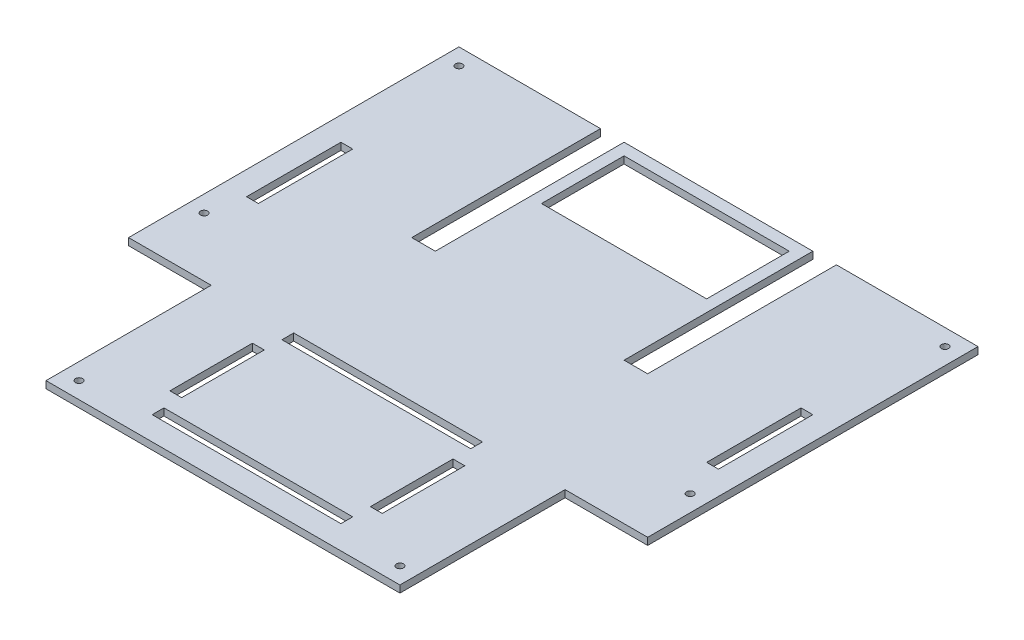
SolidWorks part; units mm, degrees
material "Pine"
ref_plane "Front Plane" through (0, 0, 0) normal (0, 0, 1) x (1, 0, 0)
ref_plane "Top Plane" through (0, 0, 0) normal (0, 1, 0) x (1, 0, 0)
ref_plane "Right Plane" through (0, 0, 0) normal (1, 0, 0) x (0, 0, -1)
sketch "Sketch4" plane through (0, 0, 0) normal (0, 1, 0) x (1, 0, 0)
  line L1 (0, 0) -> (-220, 0)
  line L2 (0, 0) -> (0, 210)
  line L3 (0, 210) -> (-220, 210)
  line L4 (-220, 0) -> (-220, 210)
  dimension "D1" = 220
  dimension "D2" = 210
extrude "Boss-Extrude1" add sketch "Sketch4" along normal blind 3
sketch "Sketch5" plane through (0, 3, 0) normal (0, 1, 0) x (1, 0, 0)
  line L1 (-220, 0) -> (-185, 0)
  line L2 (-220, 0) -> (-220, 70)
  line L3 (-220, 70) -> (-185, 70)
  line L4 (-185, 0) -> (-185, 70)
  dimension "D1" = 35
  dimension "D2" = 70
extrude "Cut-Extrude1" cut sketch "Sketch5" against normal blind 3
sketch "Sketch6" plane through (0, 3, 0) normal (0, 1, 0) x (1, 0, 0)
  line L1 (0, 0) -> (-35, 0)
  line L2 (0, 0) -> (0, 70)
  line L3 (0, 70) -> (-35, 70)
  line L4 (-35, 0) -> (-35, 70)
  dimension "D1" = 35
  dimension "D2" = 70
extrude "Cut-Extrude2" cut sketch "Sketch6" against normal blind 3
sketch "Sketch12" plane through (0, 3, 0) normal (0, 1, 0) x (1, 0, 0)
  line L2 (-35, 88) -> (-35, 80)
  line L5 (-35, 70) -> (-35, 0) construction
  dimension "D4" = 0
extrude "Cut-Extrude8" cut sketch "Sketch12" against normal blind 3 rebuild error yes
sketch "Sketch13" plane through (0, 3, 0) normal (0, 1, 0) x (1, 0, 0)
  line L4 (-215, 80) -> (-215, 88)
  dimension "D1" = 8
extrude "Cut-Extrude9" cut sketch "Sketch13" against normal blind 3 rebuild error yes
sketch "Sketch14" plane through (0, 3, 0) normal (0, 1, 0) x (1, 0, 0)
  line L0 (-110, 210) -> (-110, 0)
  line L1 (0, 210) -> (-220, 210) construction
  line L2 (-185, 0) -> (-35, 0) construction
sketch "Sketch22" plane through (0, 3, 0) normal (0, 1, 0) x (1, 0, 0)
  line L0 (-185, 0) -> (-185, 70) construction
  line L1 (-185, 0) -> (-35, 0) construction
  circle A0 centre (-178, 7) radius 1.5
  dimension "D1" = 7
  dimension "D2" = 7
sketch "Sketch24" plane through (0, 3, 0) normal (0, 1, 0) x (1, 0, 0)
  line L2 (-185, 0) -> (-35, 0) construction
  line L3 (-35, 70) -> (-35, 0) construction
  circle A0 centre (-42, 7) radius 1.5
  dimension "D1" = 7
  dimension "D2" = 7
sketch "Sketch25" plane through (0, 3, 0) normal (0, 1, 0) x (1, 0, 0)
  line L2 (0, 210) -> (-220, 210) construction
  line L3 (0, 70) -> (0, 210) construction
  circle A0 centre (-7, 203) radius 1.5
  dimension "D1" = 7
  dimension "D2" = 7
sketch "Sketch26" plane through (0, 3, 0) normal (0, 1, 0) x (1, 0, 0)
  line L2 (0, 210) -> (-220, 210) construction
  line L3 (-220, 210) -> (-220, 70) construction
  circle A0 centre (-213, 203) radius 1.5
  dimension "D1" = 7
  dimension "D2" = 7
extrude "Cut-Extrude15" cut sketch "Sketch22" against normal blind 3
extrude "Cut-Extrude16" cut sketch "Sketch26" against normal blind 3 contours A0
extrude "Cut-Extrude17" cut sketch "Sketch24" against normal blind 3
extrude "Cut-Extrude18" cut sketch "Sketch25" against normal blind 3
sketch "Sketch27" plane through (0, 3, 0) normal (0, 1, 0) x (1, 0, 0)
  line L0 (-220, 210) -> (-220, 70) construction
  line L1 (-185, 88) -> (-215, 88) construction
  circle A0 centre (-213, 95) radius 1.5
  dimension "D1" = 7
  dimension "D2" = 7
extrude "Cut-Extrude19" cut sketch "Sketch27" against normal blind 3
sketch "Sketch28" plane through (0, 3, 0) normal (0, 1, 0) x (1, 0, 0)
  line L0 (-5, 88) -> (-35, 88) construction
  line L1 (0, 70) -> (0, 210) construction
  circle A0 centre (-7, 95) radius 1.5
  dimension "D1" = 7
  dimension "D2" = 7
extrude "Cut-Extrude20" cut sketch "Sketch28" against normal blind 3
sketch "Sketch55" plane through (0, 3, 0) normal (0, 1, 0) x (1, 0, 0)
  line L1 (-52.038, 199.3694) -> (-7.038, 199.3694)
  line L2 (-52.038, 199.3694) -> (-52.038, 174.3694)
  line L3 (-52.038, 174.3694) -> (-7.038, 174.3694)
  line L4 (-7.038, 199.3694) -> (-7.038, 174.3694)
  dimension "D1" = 45
  dimension "D2" = 25
sketch "Sketch56" plane through (0, 3, 0) normal (0, 1, 0) x (1, 0, 0)
  line L0 (0, 210) -> (-220, 210) construction
  line L1 (-70, 210) -> (-60, 210)
  line L2 (-70, 210) -> (-70, 130)
  line L3 (-70, 130) -> (-60, 130)
  line L4 (-60, 210) -> (-60, 130)
  line L5 (0, 210) -> (-220, 210) construction
  line L6 (-110, 210) -> (-110, 0)
  line L7 (-185, 0) -> (-35, 0) construction
  line L8 (-150, 130) -> (-160, 130)
  line L9 (-150, 210) -> (-150, 130)
  line L10 (-150, 210) -> (-160, 210)
  line L11 (-160, 210) -> (-160, 130)
  line L13 (-145, 205) -> (-75, 205)
  line L14 (-145, 205) -> (-145, 170)
  line L15 (-145, 170) -> (-75, 170)
  line L16 (-75, 205) -> (-75, 170)
  point P6 (-110, 210)
  line M10 (0, 210) -> (-220, 210)
  dimension "D1" = 40
  dimension "D2" = 10
  dimension "D3" = 80
  dimension "D4" = 70
  dimension "D5" = 35
  dimension "D6" = 5
  dimension "D7" = 35
extrude "Cut-Extrude21" cut sketch "Sketch56" against normal blind 3 contours L14 L15 L6 L13 | L16 L13 L6 L15 | L11 L8 L9 M10 | L2 L3 L4 L1 region at (-92.5, 3, -187.5) region at (-127.5, 3, -187.5) region at (-155, 3, -170)
sketch "Sketch57" plane through (0, 3, 0) normal (0, 1, 0) x (1, 0, 0)
  line L0 (-185, 0) -> (-35, 0) construction
  line L1 (-150, 70) -> (-70, 70)
  line L2 (-150, 70) -> (-150, 65)
  line L3 (-150, 65) -> (-70, 65)
  line L4 (-70, 70) -> (-70, 65)
  line L5 (-185, 70) -> (-220, 70) construction
  line L6 (-150, 15) -> (-70, 15)
  line L7 (-150, 15) -> (-150, 10)
  line L8 (-150, 10) -> (-70, 10)
  line L9 (-70, 15) -> (-70, 10)
  line L10 (-70, 57.5) -> (-65, 57.5)
  line L11 (-70, 57.5) -> (-70, 22.5)
  line L12 (-70, 22.5) -> (-65, 22.5)
  line L13 (-65, 57.5) -> (-65, 22.5)
  line L14 (-150, 57.5) -> (-155, 57.5)
  line L15 (-150, 57.5) -> (-150, 22.5)
  line L16 (-150, 22.5) -> (-155, 22.5)
  line L17 (-155, 57.5) -> (-155, 22.5)
  line L18 (-15, 150) -> (-10, 150)
  line L19 (-15, 150) -> (-15, 110)
  line L20 (-15, 110) -> (-10, 110)
  line L21 (-10, 150) -> (-10, 110)
  line L22 (-210, 150) -> (-205, 150)
  line L23 (-210, 150) -> (-210, 110)
  line L24 (-210, 110) -> (-205, 110)
  line L25 (-205, 150) -> (-205, 110)
  line L26 (-220, 210) -> (-220, 70) construction
  line L27 (0, 70) -> (0, 210) construction
  line L28 (0, 70) -> (-35, 70) construction
  point P4 (-110, 0)
  dimension "D1" = 80
  dimension "D2" = 40
  dimension "D3" = 5
  dimension "D4" = 10
  dimension "D5" = 5
  dimension "D6" = 5
  dimension "D7" = 5
  dimension "D8" = 35
  dimension "D9" = 35
  dimension "D10" = 7.5
  dimension "D11" = 7.5
  dimension "D12" = 40
  dimension "D13" = 5
  dimension "D14" = 5
  dimension "D15" = 40
  dimension "D16" = 40
  dimension "D17" = 10
  dimension "D18" = 10
  dimension "D19" = 40
  dimension "D20" = 0
extrude "Cut-Extrude22" cut sketch "Sketch57" against normal blind 3
